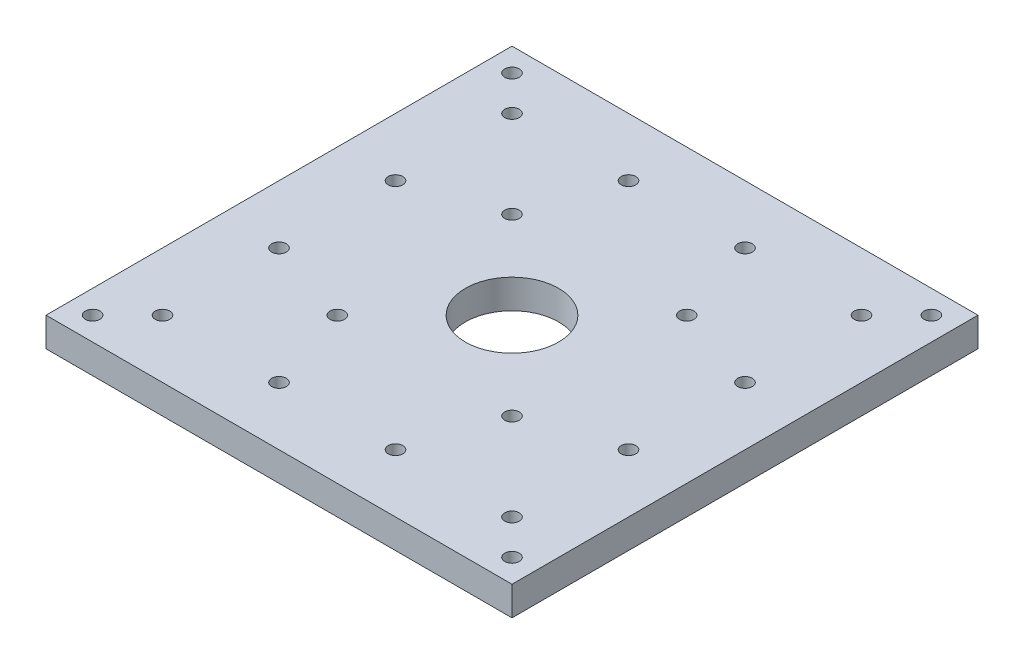
SolidWorks part; units mm, degrees
material "ABS"
ref_plane "Plan de face" through (0, 0, 0) normal (0, 0, 1) x (1, 0, 0)
ref_plane "Plan de dessus" through (0, 0, 0) normal (0, 1, 0) x (1, 0, 0)
ref_plane "Plan de droite" through (0, 0, 0) normal (1, 0, 0) x (0, 0, -1)
sketch "Esquisse1" plane through (0, 0, 0) normal (0, 1, 0) x (1, 0, 0)
  line L0 (0, 0) -> (0, 40) construction
  line L1 (-40, 40) -> (40, 40)
  line L2 (-40, 40) -> (-40, -40)
  line L3 (-40, -40) -> (40, -40)
  line L4 (40, 40) -> (40, -40)
  line L5 (0, 0) -> (40, 0) construction
  circle A0 centre (-15, 15) radius 1.25
  circle A1 centre (15, 15) radius 1.25
  circle A2 centre (-15, -15) radius 1.25
  circle A3 centre (15, -15) radius 1.25
  circle A4 centre (-36, 36) radius 1.25
  circle A5 centre (36, 36) radius 1.25
  circle A6 centre (36, -36) radius 1.25
  circle A7 centre (-36, -36) radius 1.25
  circle A8 centre (0, 0) radius 8
  dimension "D4" = 2.5
  dimension "D7" = 16
  dimension "D1" = 80
  dimension "D2" = 15
  dimension "D3" = 15
  dimension "D5" = 4
  dimension "D6" = 4
extrude "Extrusion1" add sketch "Esquisse1" along normal blind 5
sketch "Esquisse2" plane through (0, 5, 0) normal (0, 1, 0) x (1, 0, 0)
  circle A0 centre (-30, 30) radius 1.25
  dimension "D1" = 2.5
  dimension "D2" = 30
  dimension "D3" = 30
extrude "Enlèv. mat.-Extru.1" cut sketch "Esquisse2" against normal through all
pattern_linear "Répétition linéaire1" count 4 spacing 20 along (0, 0, 1) count 4 spacing 20 along (1, 0, 0) skipping (1, 1), (1, 2), (2, 1), (2, 2) of "Enlèv. mat.-Extru.1"
